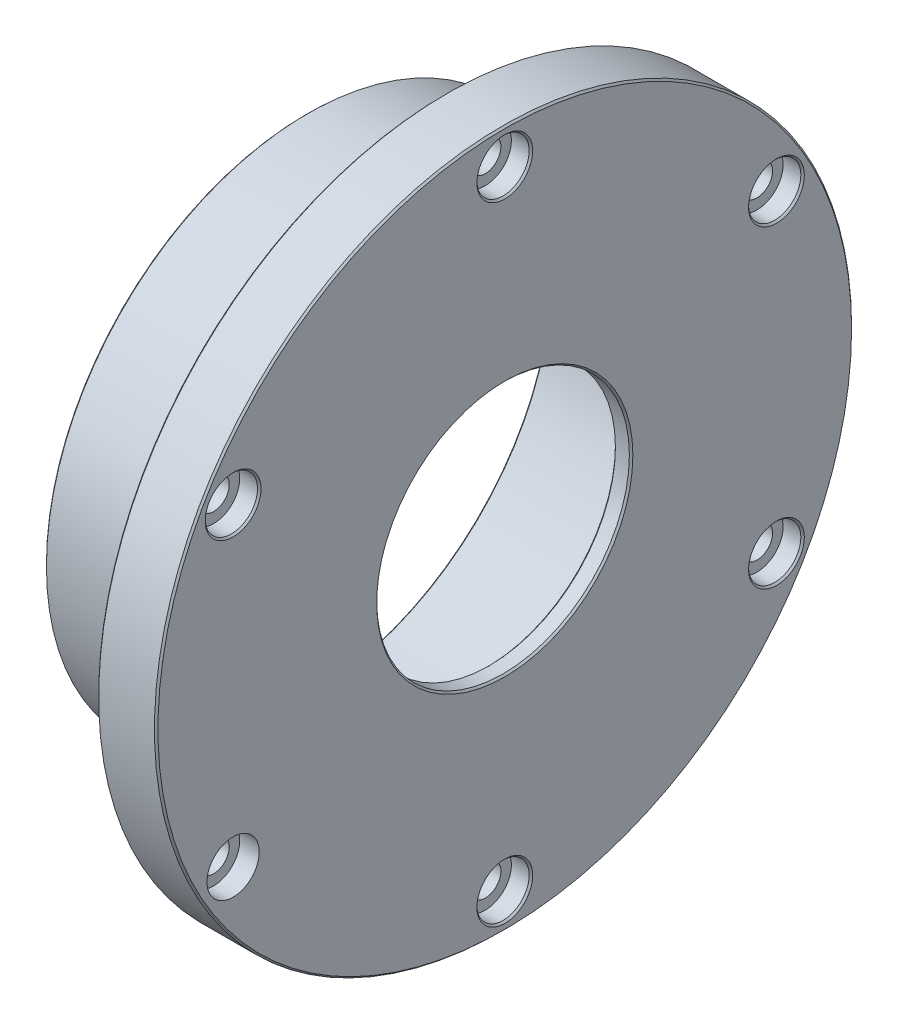
SolidWorks part; units mm, degrees
ref_plane "Front Plane" through (0, 0, 0) normal (0, 0, 1) x (1, 0, 0)
ref_plane "Top Plane" through (0, 0, 0) normal (0, 1, 0) x (1, 0, 0)
ref_plane "Right Plane" through (0, 0, 0) normal (1, 0, 0) x (0, 0, -1)
sketch "Sketch1" plane through (0, 0, 0) normal (0, 0, 1) x (1, 0, 0)
  line L0 (-15.2619, -33.1832) -> (53.5176, -33.1832)
  line L1 (22.9387, 66.8168) -> (39.9387, 66.8168)
  line L2 (-17.0613, 41.8168) -> (-17.0613, 36.8168)
  line L3 (34.9387, 3.0668) -> (39.9387, 3.0668)
  line L5 (39.9387, 66.8168) -> (39.9387, 3.0668)
  line L16 (-17.0613, 41.8168) -> (22.9387, 41.8168)
  line L17 (22.9387, 66.8168) -> (22.9387, 41.8168)
  line L20 (-17.0613, 36.8168) -> (21.9387, 36.8168)
  line L21 (21.9387, 26.8168) -> (21.9387, 36.8168)
  line L22 (21.9387, 26.8168) -> (26.9387, 26.8168)
  line L25 (34.9387, 21.8168) -> (34.9387, 3.0668)
  line L32 (34.9387, 21.8168) -> (26.9387, 21.8168)
  line L33 (26.9387, 26.8168) -> (26.9387, 21.8168)
  dimension "D1" = 63.75
  dimension "D2" = 40
  dimension "D3" = 36.25
  dimension "D4" = 39
  dimension "D5" = 10
  dimension "D6" = 5
  dimension "D7" = 17
  dimension "D8" = 5
  dimension "D9" = 5
  dimension "D11" = 8
revolve "Revolve1" add sketch "Sketch1" angle 360 about L0 region at (26.5782, 40.7761, 0)
sketch "Sketch2" plane through (39.9387, 0, 0) normal (1, 0, 0) x (0, 0, -1)
  line L0 (0, -33.1832) -> (0, 56.8168)
  line L1 (0, -33.1832) -> (77.9423, 11.8168)
  line L2 (0, -33.1832) -> (77.9423, -78.1832)
  line L3 (0, -33.1832) -> (0, -123.1832)
  line L4 (0, -33.1832) -> (-77.9423, -78.1832)
  line L5 (0, -33.1832) -> (-77.9423, 11.8168)
  point P6 (0, 56.8168)
  point P9 (0, -33.1832)
  point P24 (-77.9423, 11.8168)
  point P27 (-77.9423, -78.1832)
  point P30 (0, -123.1832)
  point P33 (77.9423, -78.1832)
  point P36 (77.9423, 11.8168)
  dimension "D1" = 90
  dimension "D2" = 6
hole_wizard "CBORE for M8 Hex Socket Thin Head Cap Screw1" positions "Sketch2" profile "Sketch3" counterbore size "M8" standard "DIN"
sketch "Sketch3" plane through (39.9387, 11.8168, -77.9423) normal (0, 1, 0) x (0, 0, -1)
  line L0 (0, 0) -> (0, 19.7039)
  line L1 (0, 19.7039) -> (4.5, 17)
  line L2 (4.5, 17) -> (4.5, 5.6)
  line L3 (4.5, 5.6) -> (7.5, 5.6)
  line L4 (7.5, 5.6) -> (7.5, 0)
  line L5 (7.5, 0) -> (0, 0)
  line L10 (0, 19.7039) -> (-4.5, 17) construction
  line L11 (0, -6.35) -> (0, 107.95) construction
  dimension "Hole Dia." = 9
  dimension "Hole Depth" = 17
  dimension "C'Bore Dia." = 15
  dimension "C'Bore Depth" = 5.6
  dimension "Drill Angle" = 118
chamfer "Chamfer1" distance 0.5 angle 45 19 edges at (22.9387, -33.1832, 100) (-17.0613, -33.1832, 75) (22.9387, -123.1832, -4.5) (22.9387, -78.1832, -82.4423) (22.9387, 11.8168, -82.4423) (22.9387, 56.8168, -4.5) (22.9387, 11.8168, 73.4423) (22.9387, -78.1832, 73.4423) (39.9387, -123.1832, -7.5) (39.9387, -78.1832, -85.4423) (39.9387, 11.8168, -85.4423) (39.9387, 56.8168, -7.5) (39.9387, 11.8168, 70.4423) (-17.0613, -33.1832, 70) (39.9387, -33.1832, 36.25) (39.9387, -33.1832, 100) (34.9387, -33.1832, 36.25) (26.9387, -33.1832, 55) (21.9387, -33.1832, 60)
